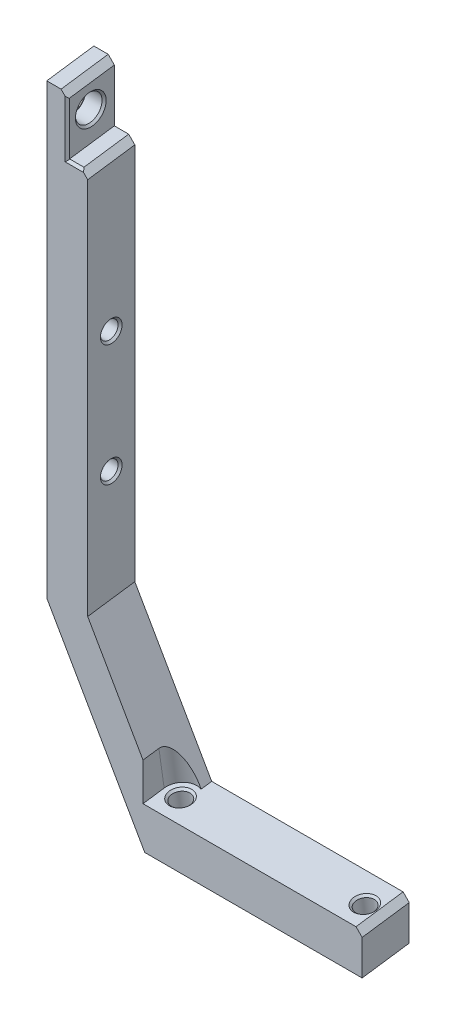
SolidWorks part; units mm, degrees
ref_plane "Top" through (0, 0, 0) normal (0, 0, 1) x (1, 0, 0)
ref_plane "Front" through (0, 0, 0) normal (0, 1, 0) x (1, 0, 0)
ref_plane "Right" through (0, 0, 0) normal (1, 0, 0) x (0, 0, -1)
sketch "Sketch4" plane through (0, 0, 0) normal (1, 0, 0) x (0, 0, -1)
  line L1 (0, 0) -> (11.5, 0)
  line L2 (0, 0) -> (0, 144)
  line L3 (0, 144) -> (11.5, 144)
  line L4 (11.5, 0) -> (11.5, 144)
  dimension "D1" = 11.5
  dimension "D2" = 144
extrude "Boss-Extrude2" add sketch "Sketch4" along normal blind 10
sketch "Sketch6" plane through (10, 0, 0) normal (1, 0, 0) x (0, 0, -1)
  line L0 (5.75, 0) -> (11.5, 0.8081)
  line L1 (0, 0) -> (11.5, 0) construction
  line L2 (11.5, 0) -> (11.5, 144) construction
  line L3 (11.5, 0.8081) -> (10.1083, 10.7108)
  line L4 (10.1083, 10.7108) -> (0.2056, 9.3191)
  line L5 (0.2056, 9.3191) -> (1.5973, -0.5836)
  line L6 (1.5973, -0.5836) -> (5.75, 0)
  line L7 (0, 144) -> (0, 0) construction
  dimension "D1" = 10
  dimension "D2" = 10
  dimension "D3" = 82
extrude "Boss-Extrude3" add sketch "Sketch6" along normal blind 67 and the other way blind 10
sketch "Sketch26" plane through (0, 1.6006, -11.3886) normal (0, 0.1392, -0.9903) x (-1, 0, 0)
  line L0 (-23, -0.8002) -> (0, 39.0369)
  line L1 (-10, -0.8002) -> (-77, -0.8002) construction
  line L2 (0, -1.6005) -> (0, 140.9981) construction
  line L3 (0, 39.0369) -> (-8.6603, 44.0369)
  line L5 (-8.6603, 44.0369) -> (-31.6603, 4.1998)
  line L7 (-23, -0.8002) -> (-31.6603, 4.1998)
  dimension "D1" = 23
  dimension "D2" = 60
  dimension "D3" = 10
extrude "Boss-Extrude6" add sketch "Sketch26" along normal up to surface and the other way up to surface up to face at (6, 57.7616, -11.5) other way up to face at (5, 72, 0)
sketch "Sketch7" plane through (10, 0, 0) normal (1, 0, 0) x (0, 0, -1)
  line L0 (-3.1126, -1.2456) -> (11.8209, -3.029)
  line L2 (11.8209, -3.029) -> (11.8209, 0.8532)
  line L3 (11.8209, 0.8532) -> (-3.1126, -1.2456)
  line L4 (1.5973, -0.5836) -> (11.5, 0.8081) construction
extrude "Cut-Extrude2" cut sketch "Sketch7" against normal blind 10
sketch "Sketch8" plane through (0, 9.1102, 1.2804) normal (0, 0.9903, 0.1392) x (1, 0, 0)
  line L0 (28.7735, 1.5005) -> (77, 1.5005) construction
  line L1 (77, 11.5005) -> (77, 1.5005) construction
  circle A0 centre (72.5, 6.5005) radius 2.25
  circle A1 centre (27.5, 6.5005) radius 2.25
  dimension "D2" = 4.5
  dimension "D3" = 4.5
  dimension "D1" = 45
  dimension "D4" = 5
  dimension "D5" = 4.5
extrude "Cut-Extrude3" cut sketch "Sketch8" against normal through all
sketch "Sketch11" plane through (0, 9.1102, 1.2804) normal (0, 0.9903, 0.1392) x (1, 0, 0)
  line L0 (23.5, 6.5005) -> (23.5, 0)
  line L1 (23.5, 0) -> (31.5, 0)
  line L3 (31.5, 0) -> (31.5, 6.5005)
  line L4 (10, 0) -> (0, 0) construction
  circle A0 centre (27.5, 6.5005) radius 4 construction
  arc A1 (31.5, 6.5005) -> (23.5, 6.5005) centre (27.5, 6.5005) ccw
  dimension "D1" = 8
sketch "Sketch12" plane through (77, 0, 0) normal (1, 0, 0) x (0, 0, -1)
  line L5 (0.2056, 9.3191) -> (10.1083, 10.7108) construction
  line L13 (1.5973, -0.5836) -> (0, -0.8081)
  line L14 (0, -0.8081) -> (0, 9.2902)
  line L16 (1.5973, -0.5836) -> (11.5, 0.8081) construction
  line L17 (0, 21.9298) -> (0, 0) construction
  line L18 (11.5, 0.8081) -> (11.5, 10.9064)
  line L20 (11.5, 10.9064) -> (10.1083, 10.7108)
  line L21 (10.1083, 10.7108) -> (11.5, 0.8081)
  line L22 (10.1083, 10.7108) -> (0.2056, 9.3191) construction
  line L23 (11.5, 0.8081) -> (11.5, 23.5461) construction
  line L25 (11.5, 0.8081) -> (10.1083, 10.7108) construction
  line L26 (0, 9.2902) -> (0.2056, 9.3191)
  line L27 (0.2056, 9.3191) -> (1.5973, -0.5836)
  line L28 (0.2056, 9.3191) -> (1.5973, -0.5836) construction
extrude "Boss-Extrude4" add sketch "Sketch12" against normal up to surface (77 mm away) up to face at (0, 48.0374, -4.3521)
sketch "Sketch13" plane through (10, 0, 0) normal (1, 0, 0) x (0, 0, -1)
  line L0 (11.5, 144) -> (11.5, 152)
  line L1 (11.5, 152) -> (0, 150.3838)
  line L2 (0, 150.3838) -> (0, 144)
  line L3 (0, 144) -> (11.5, 144)
  line L4 (11.5, 10.9064) -> (0, 9.2902) construction
  dimension "D1" = 8
extrude "Boss-Extrude5" add sketch "Sketch13" against normal blind 10
sketch "Sketch14" plane through (10, 0, 0) normal (1, 0, 0) x (0, 0, -1)
  line L0 (11.5, 10.9064) -> (11.5, 23.5461) construction
  circle A0 centre (5.75, 144) radius 3.25
  dimension "D2" = 6.5
  dimension "D1" = 8
  dimension "D3" = 5.75
extrude "Cut-Extrude5" cut sketch "Sketch14" against normal blind 10
sketch "Sketch18" plane through (10, 0, 0) normal (1, 0, 0) x (0, 0, -1)
  line L0 (5.75, 99.6) -> (5.75, 70)
  line L1 (11.5, 10.9064) -> (11.5, 23.5461) construction
  dimension "D1" = 5.75
  dimension "D2" = 29.6
  dimension "D3" = 70
hole_wizard "M4 Clearance Hole1" positions "Sketch19" profile "Sketch20" hole size "M4" standard "DIN" end condition through all
sketch "Sketch19" plane through (10, 0, 0) normal (1, 0, 0) x (0, 0, -1)
  point P0 (5.75, 70)
  point P3 (5.75, 99.6)
sketch "Sketch20" plane through (10, 70, -5.75) normal (0, 1, 0) x (0, 0, -1)
  line L0 (0, 0) -> (0, 10)
  line L1 (0, 10) -> (2.15, 10)
  line L2 (2.15, 10) -> (2.15, 0)
  line L5 (2.15, 0) -> (0, 0)
  line L11 (0, -6.35) -> (0, 107.95) construction
  dimension "Thru Hole Dia." = 4.3
  dimension "Thru Hole Depth" = 10
sketch "Sketch24" plane through (10, 0, 0) normal (1, 0, 0) x (0, 0, -1)
  line L0 (11.5, 152) -> (0, 150.3838)
  line L1 (0, 150.3838) -> (0, 136)
  line L2 (0, 150.3838) -> (0, 42.1264) construction
  line L3 (0, 136) -> (11.5, 137.6162)
  line L4 (11.5, 10.9064) -> (11.5, 23.5461) construction
  line L5 (11.5, 137.6162) -> (11.5, 152)
  circle A0 centre (5.75, 144) radius 3.25 construction
  dimension "D1" = 8
extrude "Cut-Extrude7" cut sketch "Sketch24" against normal blind 5
chamfer "Chamfer2" distance 0.5 angle 45 8 edges at (10, 70, -7.9) (0, 70, -7.9) (10, 99.6, -7.9) (0, 99.6, -7.9) (0, 144, -9) (72.5, 9.7018, -2.9288) (72.5, 0.4254, -8.7768) (5, 144, -9)
chamfer "Chamfer5" distance 0.5 angle 45 2 edges at (7.5, 136, 0) (5, 143.1919, 0) first distance on face at (12.4088, 13.5034, 0)
chamfer "Chamfer6" distance 1.5 angle 45 2 edges at (5, 151.227, -6) (10, 136.849, -6.0409)
chamfer "Chamfer7" distance 1.5 angle 45 1 edges at (77, 10.0983, -5.75)
sketch "Sketch28" plane through (0, 0.0079, -11.5) normal (0, 0, 1) x (-1, 0, 0)
  line L0 (-217.25, 338.9571) -> (8.299, 9.2449)
  line L1 (8.299, 9.2449) -> (8.299, -55.5445)
  line L2 (8.299, -55.5445) -> (-217.25, 338.9571)
  line L3 (-10, -23.5382) -> (-17.2265, -10.8985) construction
  point P2 (-33.19, 17.0228)
extrude "Cut-Extrude8" cut sketch "Sketch28" against normal through all and the other way through all
ref_plane "Plane1" through (87, 0, 0) normal (1, 0, 0) x (0, 0, -1)
extrude "Cut-Extrude9" cut sketch "Sketch11" along normal through all
chamfer "Chamfer10" distance 0.5 angle 45 2 edges at (27.5, 9.7018, -2.9288) (27.5, 0.4254, -8.7768)
